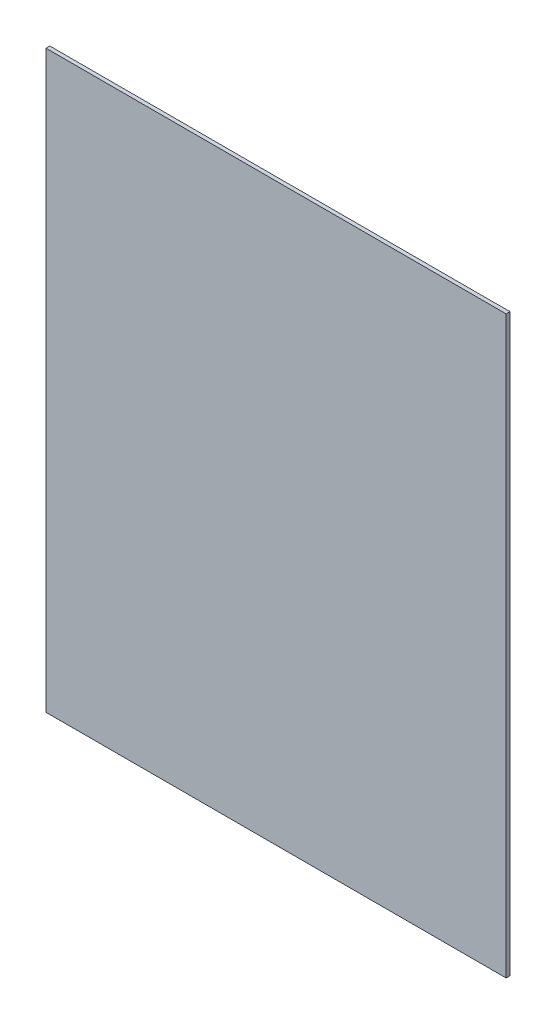
SolidWorks part; units mm, degrees
ref_plane "Ön Düzlem" through (0, 0, 0) normal (0, 0, 1) x (1, 0, 0)
ref_plane "Üst Düzlem" through (0, 0, 0) normal (0, 1, 0) x (1, 0, 0)
ref_plane "Sağ Düzlem" through (0, 0, 0) normal (1, 0, 0) x (0, 0, -1)
sketch "Çizim1" plane through (0, 0, 0) normal (0, 0, 1) x (1, 0, 0)
  line L1 (0, 0) -> (1200, 0)
  line L2 (0, 0) -> (0, -1500)
  line L3 (0, -1500) -> (1200, -1500)
  line L4 (1200, 0) -> (1200, -1500)
  dimension "D1" = 1200
  dimension "D2" = 1500
base flange "Taban-Flanş1" sketch "Çizim1" thickness 10 reverse thickness direction no parameters "D1"=4
sketch "Büküm-Çizgileri1" [suppressed] plane through (0, 0, 0) normal (0, 1, 0) x (1, 0, 0)
sketch "Sınırlandırma-Kutusu1" [suppressed] plane through (0, 0, 0) normal (0, 1, 0) x (1, 0, 0)
sheet metal parameters "Sac-Levha1" thickness 10 parameters "D1"=4
flat pattern "Düz-Çoğaltma1" [suppressed]
sketch "Büküm-Çizgileri2" plane through (0, 0, 0) normal (0, 1, 0) x (1, 0, 0)
sketch3d "Sınırlandırma-Kutusu2" [suppressed]
  line L0 (1200, 0, 0) -> (1200, -1500, 0) construction
  line L1 (0, 0, 0) -> (0, -1500, 0) construction
  line L2 (1200, 0, 0) -> (0, 0, 0) construction
  line L3 (1200, -1500, 0) -> (0, -1500, 0) construction
